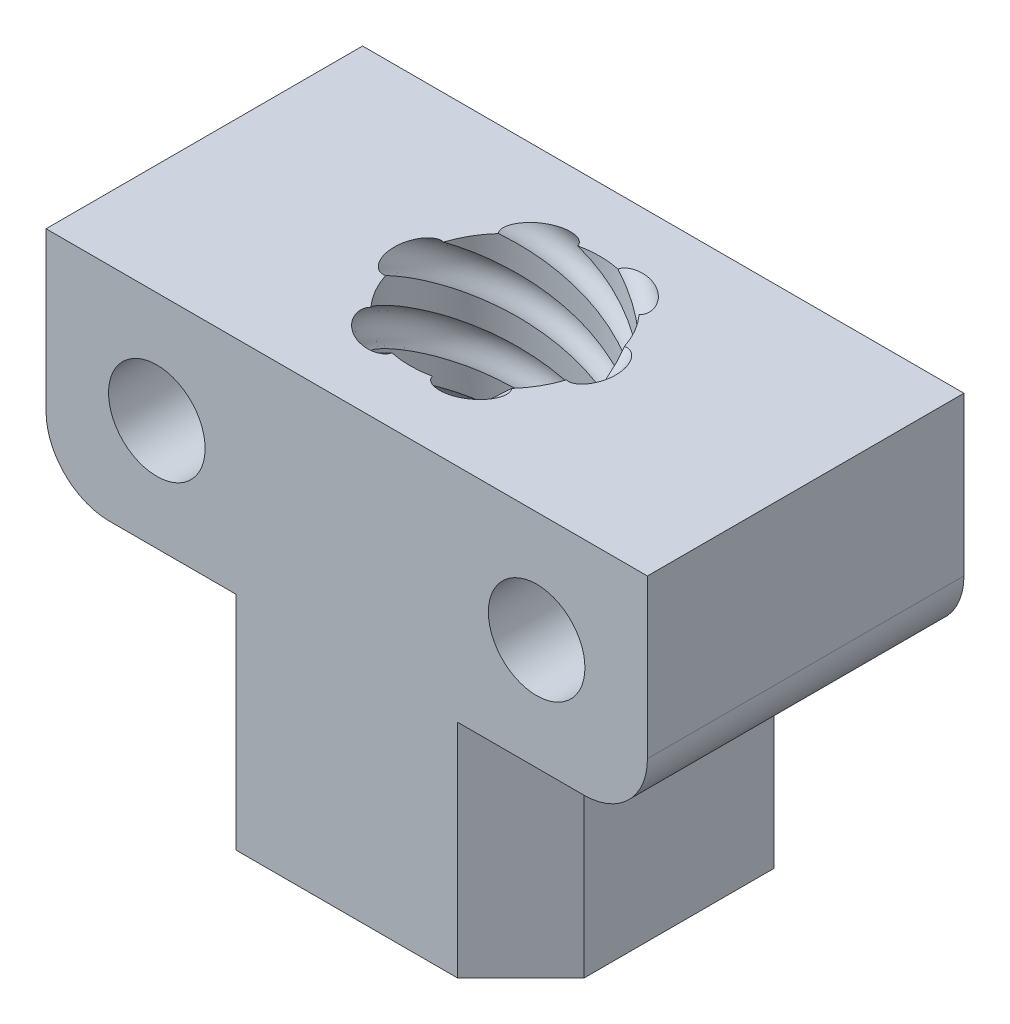
SolidWorks part; units mm, degrees
ref_plane "前视基准面" through (0, 0, 0) normal (0, 0, 1) x (1, 0, 0)
ref_plane "上视基准面" through (0, 0, 0) normal (0, 1, 0) x (1, 0, 0)
ref_plane "右视基准面" through (0, 0, 0) normal (1, 0, 0) x (0, 0, -1)
other "Configuration Table"
sketch "草图1" plane through (0, 0, 0) normal (0, 0, 1) x (1, 0, 0)
  line L0 (-5.5, -4.7661) -> (5.5, -4.7661)
  line L1 (5.5, -4.7661) -> (5.5, 2.2339)
  line L2 (5.5, 2.2339) -> (9.5, 2.2339)
  line L3 (9.5, 2.2339) -> (9.5, 9.2339)
  line L4 (9.5, 9.2339) -> (-9.5, 9.2339)
  line L5 (-9.5, 9.2339) -> (-9.5, 2.2339)
  line L6 (-9.5, 2.2339) -> (-5.5, 2.2339)
  line L7 (-5.5, 2.2339) -> (-5.5, -4.7661)
  line L8 (0, 15.2688) -> (0, -18.8942) construction
  dimension "D1" = 19
  dimension "D2" = 14
  dimension "D3" = 7
  dimension "D4" = 11
extrude "凸台-拉伸1" add sketch "草图1" along normal blind 10
sketch "草图2" plane through (0, 9.2339, 0) normal (0, 1, 0) x (1, 0, 0)
  line L0 (0, 0) -> (0, -10) construction
  line L1 (9.5, 0) -> (-9.5, 0) construction
  line L2 (9.5, -10) -> (-9.5, -10) construction
  line L3 (-9.5, -5) -> (9.5, -5) construction
  line L4 (-9.5, -10) -> (-9.5, 0) construction
  line L5 (9.5, -10) -> (9.5, 0) construction
  circle A0 centre (0, -5) radius 3
  dimension "D1" = 6
extrude "切除-拉伸1" cut sketch "草图2" against normal blind 26
sketch "草图3" plane through (0, 9.2339, 0) normal (0, 1, 0) x (1, 0, 0)
  circle A1 centre (0, -5) radius 3
  dimension "D1" = 6
curve "螺旋线/涡状线1" pitch 12 height 120 turns 10
sketch "草图39" plane through (0, 9.2339, 0) normal (0, 1, 0) x (1, 0, 0)
  circle A0 centre (0, -5) radius 3
  circle A1 centre (0, -5) radius 3 construction
curve "螺旋线/涡状线2" pitch 12 height 24 turns 2
sketch "草图51" plane through (0, 9.2339, 0) normal (0, 1, 0) x (1, 0, 0)
  circle A0 centre (0, -5) radius 3
  circle A1 centre (0, -5) radius 3 construction
curve "螺旋线/涡状线3" pitch 12 height 24 turns 2
sketch "草图52" plane through (0, 9.2339, 0) normal (0, 1, 0) x (1, 0, 0)
  circle A0 centre (0, -5) radius 3 construction
  circle A1 centre (0, -5) radius 3
curve "螺旋线/涡状线4" pitch 12 height 24 turns 2
sketch "草图53" plane through (0, 9.2339, 0) normal (0, 1, 0) x (1, 0, 0)
  circle A0 centre (0, -5) radius 3 construction
  circle A1 centre (0, -5) radius 3
curve "螺旋线/涡状线5" pitch 12 height 24 turns 2
sketch "草图54" plane through (0, 9.2339, 0) normal (0, 1, 0) x (1, 0, 0)
  circle A0 centre (0, -5) radius 3 construction
  circle A1 centre (0, -5) radius 3
curve "螺旋线/涡状线6" pitch 12 height 24 turns 2
sweep "切除-扫描2" cut path "螺旋线/涡状线1" parameters "D3"=1
sweep "切除-扫描3" cut path "螺旋线/涡状线2" circular profile diameter 1 parameters "D3"=1
sweep "切除-扫描4" cut path "螺旋线/涡状线3" circular profile diameter 1 parameters "D3"=1
sweep "切除-扫描5" cut path "螺旋线/涡状线4" circular profile diameter 1 parameters "D3"=1
sweep "切除-扫描6" cut path "螺旋线/涡状线5" circular profile diameter 1 parameters "D3"=1
sweep "切除-扫描7" cut path "螺旋线/涡状线6" circular profile diameter 1 parameters "D3"=1
sketch "草图15" plane through (0, 0, 10) normal (0, 0, 1) x (1, 0, 0)
  line L0 (0, 15.2315) -> (0, -15.8761) construction
  line L1 (9.5, 9.2339) -> (-9.5, 9.2339) construction
  circle A0 centre (-6, 5.7339) radius 1.525
  circle A1 centre (6, 5.7339) radius 1.525
  dimension "D3" = 3.05
  dimension "D1" = 6
  dimension "D2" = 3.5
extrude "切除-拉伸2" cut sketch "草图15" against normal blind 26
fillet "圆角1" radius 2 2 edges at (9.5, 2.2339, 5) (-9.5, 2.2339, 5)
sketch "草图18" plane through (0, 0, 10) normal (0, 0, 1) x (1, 0, 0)
  line L0 (0, 9.2339) -> (0, -2.7661) construction
  line L8 (-5.5, -4.7661) -> (5.5, -4.7661)
  line L9 (-5.5, 2.2339) -> (-5.5, -4.7661)
  line L10 (5.5, 2.2339) -> (7.5, 2.2339)
  line L11 (9.5, 4.2339) -> (9.5, 9.2339)
  line L12 (9.5, 9.2339) -> (-9.5, 9.2339)
  line L13 (-9.5, 9.2339) -> (-9.5, 4.2339)
  line L14 (-7.5, 2.2339) -> (-5.5, 2.2339)
  line L15 (-5.5, 2.2339) -> (-5.5, -4.7661)
  line L16 (-5.5, -4.7661) -> (5.5, -4.7661)
  line L18 (5.5, 2.2339) -> (7.5, 2.2339)
  line L19 (9.5, 4.2339) -> (9.5, 9.2339)
  line L20 (9.5, 9.2339) -> (-9.5, 9.2339)
  line L21 (-9.5, 9.2339) -> (-9.5, 4.2339)
  line L22 (-7.5, 2.2339) -> (-5.5, 2.2339)
  line L25 (5.5, -4.7661) -> (5.5, 2.2339)
  line L26 (5.5, -4.7661) -> (5.5, 2.2339)
  circle A0 centre (-6, 5.7339) radius 1.525 construction
  circle A1 centre (-6, 5.7339) radius 1.525
  circle A2 centre (6, 5.7339) radius 1.525 construction
  arc A3 (7.5, 2.2339) -> (9.5, 4.2339) centre (7.5, 4.2339) ccw
  arc A4 (-9.5, 4.2339) -> (-7.5, 2.2339) centre (-7.5, 4.2339) ccw
  circle A7 centre (6, 5.7339) radius 1.525
  arc A8 (-9.5, 4.2339) -> (-7.5, 2.2339) centre (-7.5, 4.2339) ccw construction
  arc A9 (-9.5, 4.2339) -> (-7.5, 2.2339) centre (-7.5, 4.2339) ccw
  arc A10 (7.5, 2.2339) -> (9.5, 4.2339) centre (7.5, 4.2339) ccw construction
  arc A11 (7.5, 2.2339) -> (9.5, 4.2339) centre (7.5, 4.2339) ccw
  dimension "D1" = 0
  dimension "D2" = 3.05
  dimension "D7" = 3.05
  dimension "D10" = 2
  dimension "D3" = 19
  dimension "D4" = 7.5
  dimension "D6" = 9.5
  dimension "D8" = 11
  dimension "D9" = 14
sketch "草图20" plane through (0, -4.7661, 0) normal (0, -1, 0) x (1, 0, 0)
  line L0 (0, 4) -> (0, 0) construction
  line L1 (-5.5, 10) -> (5.5, 10) construction
  line L14 (-5.5, 10) -> (-5.5, 0)
  line L16 (-5.5, 0) -> (5.5, 0)
  line L18 (5.5, 0) -> (5.5, 10)
  line L20 (5.5, 10) -> (-5.5, 10)
  line L22 (-5.5, 10) -> (-5.5, 0)
  line L24 (-5.5, 0) -> (5.5, 0)
  line L26 (5.5, 0) -> (5.5, 10)
  line L28 (5.5, 10) -> (-5.5, 10)
  circle A2 centre (0, 5) radius 3 construction
  circle A3 centre (0, 5) radius 3
  point P6 (0, 10)
  dimension "D4" = 0
  dimension "D6" = 6
  dimension "D2" = 5.5
sketch "草图21" plane through (0, 9.2339, 0) normal (0, 1, 0) x (1, 0, 0)
  line L4 (9.5, 0) -> (-9.5, 0)
  line L5 (-9.5, 0) -> (-9.5, -10)
  line L6 (-9.5, -10) -> (9.5, -10)
  line L7 (9.5, -10) -> (9.5, 0)
  line L8 (9.5, 0) -> (-9.5, 0)
  line L9 (-9.5, 0) -> (-9.5, -10)
  line L10 (-9.5, -10) -> (9.5, -10)
  line L11 (9.5, -10) -> (9.5, 0)
  circle A0 centre (0, -5) radius 3 construction
  circle A1 centre (0, -5) radius 3
  dimension "D4" = 6
  dimension "D2" = 19
  dimension "D3" = 10
  dimension "D1" = 0
chamfer "倒角1" distance 2 angle 45 4 edges at (5.5, -1.2661, 0) (-5.5, -1.2661, 0) (5.5, -1.2661, 10) (-5.5, -1.2661, 10)
